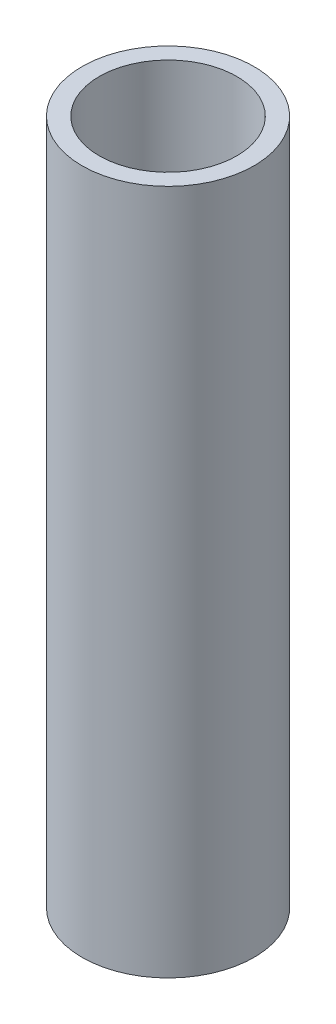
SolidWorks part; units mm, degrees
ref_plane "Alzado" through (0, 0, 0) normal (0, 0, 1) x (1, 0, 0)
ref_plane "Planta" through (0, 0, 0) normal (0, 1, 0) x (1, 0, 0)
ref_plane "Vista lateral" through (0, 0, 0) normal (1, 0, 0) x (0, 0, -1)
sketch "Croquis1" plane through (0, 0, 0) normal (0, 1, 0) x (1, 0, 0)
  circle A0 centre (0, 0) radius 5
  circle A1 centre (0, 0) radius 4
  dimension "D1" = 10
  dimension "D2" = 8
extrude "Saliente-Extruir1" add sketch "Croquis1" along normal blind 39.86
